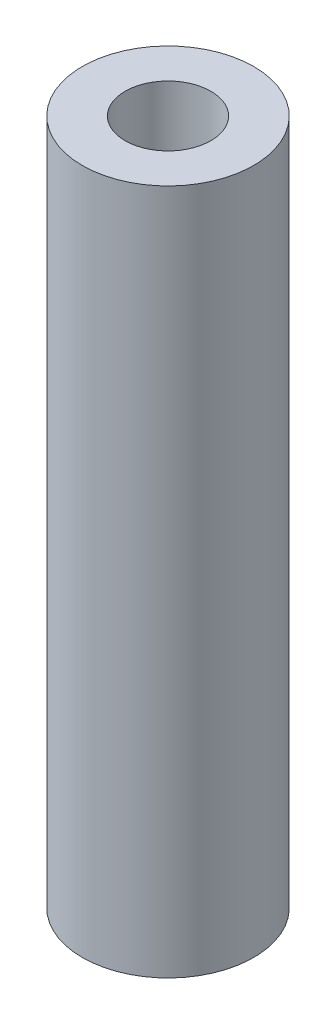
SolidWorks part; units mm, degrees
ref_plane "Front Plane" through (0, 0, 0) normal (0, 0, 1) x (1, 0, 0)
ref_plane "Top Plane" through (0, 0, 0) normal (0, 1, 0) x (1, 0, 0)
ref_plane "Right Plane" through (0, 0, 0) normal (1, 0, 0) x (0, 0, -1)
sketch "Sketch1" plane through (0, 0, 0) normal (0, 1, 0) x (1, 0, 0)
  circle A0 centre (0, 0) radius 2.5
  circle A1 centre (0, 0) radius 1.25
  dimension "D1" = 2.5
  dimension "D2" = 5
extrude "Boss-Extrude1" add sketch "Sketch1" along normal blind 20
